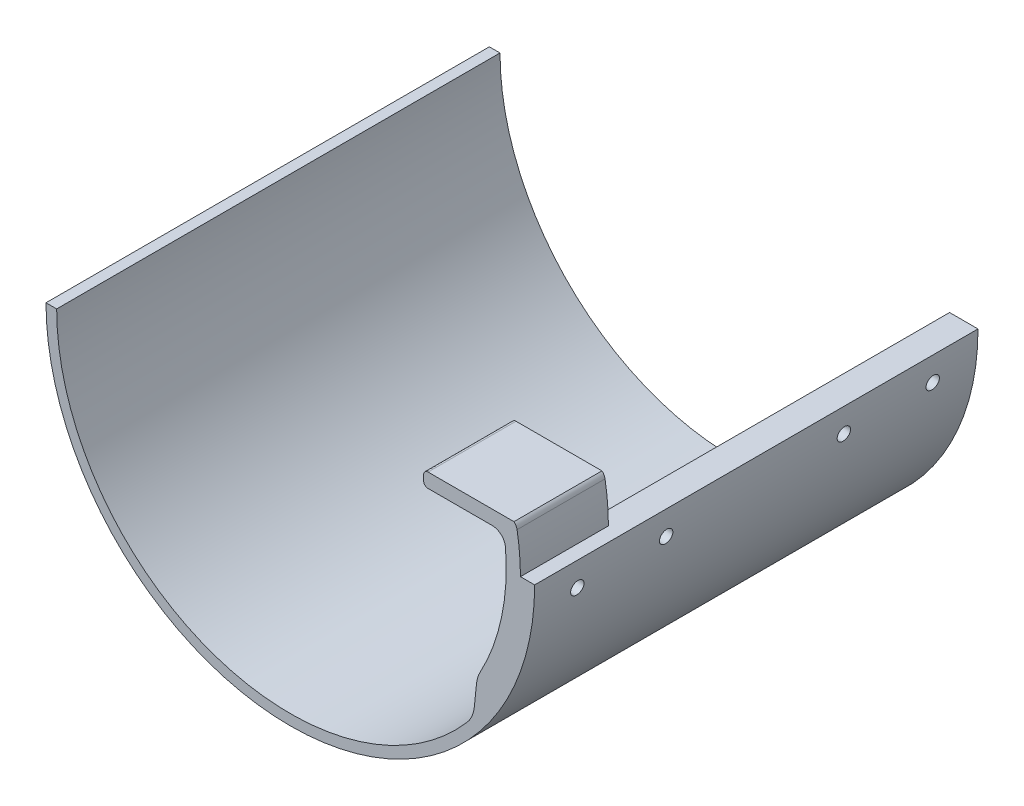
SolidWorks part; units mm, degrees
ref_plane "前视基准面" through (0, 0, 0) normal (0, 0, 1) x (1, 0, 0)
ref_plane "上视基准面" through (0, 0, 0) normal (0, 1, 0) x (1, 0, 0)
ref_plane "右视基准面" through (0, 0, 0) normal (1, 0, 0) x (0, 0, -1)
other "Configuration Table"
sketch "草图1" plane through (0, 0, 0) normal (0, 0, 1) x (1, 0, 0)
  line L0 (-55, 0) -> (-52.6, 0)
  line L1 (51.8, 0) -> (55, 0)
  line L2 (-52.6, 0) -> (51.8, 0) construction
  line L5 (41.9103, -25.796) -> (41.4208, -30.58)
  line L6 (0, 0) -> (0, 10) construction
  line L7 (0, 10) -> (31, 10) construction
  line L9 (30, 9) -> (30, 7.8)
  line L10 (31, 6.8) -> (45.4414, 6.8)
  line L11 (31, 10) -> (50.344, 10)
  arc A0 (-55, 0) -> (55, 0) centre (0, 0) ccw
  arc A1 (-52.6, 0) -> (39.7466, -34.4524) centre (0, 0) ccw
  arc A2 (51.0485, 8.7916) -> (51.8, 0) centre (0, 0) cw
  arc A3 (42.7207, -23.1711) -> (48.431, 4.05) centre (0, 0) ccw
  arc A4 (41.4208, -30.58) -> (39.7466, -34.4524) centre (34.4571, -29.8675) cw
  arc A5 (41.9103, -25.796) -> (42.7207, -23.1711) centre (48.8739, -26.5085) cw
  arc A6 (48.431, 4.05) -> (45.4414, 6.8) centre (45.4414, 3.8) ccw
  arc A7 (51.0485, 8.7916) -> (50.344, 10) centre (49.0775, 8.4521) ccw
  arc A8 (31, 6.8) -> (30, 7.8) centre (31, 7.8) cw
  arc A9 (30, 9) -> (31, 10) centre (31, 9) cw
  point P16 (42.0579, -24.3536)
  point P25 (52.0183, 10)
  point P28 (30, 6.8)
  point P31 (30.5845, 10)
  dimension "D1" = 110
  dimension "D2" = 105.2
  dimension "D3" = 97.2
  dimension "D6" = 7
  dimension "D9" = 3
  dimension "D10" = 2
  dimension "D11" = 1
  dimension "D12" = 1
  dimension "D14" = 51.8
  dimension "D5" = 31
  dimension "D7" = 3.2
  dimension "D8" = 21.4339
  dimension "D13" = 10
extrude "凸台-拉伸1" add sketch "草图1" along normal blind 99.8
sketch "草图4" plane through (0, 0, 99.8) normal (0, 0, 1) x (1, 0, 0)
  line L0 (55, 0) -> (0, 0)
  line L1 (0, 0) -> (50.017, 22.8758)
  arc A0 (55, 0) -> (50.017, 22.8758) centre (0, 0) ccw
sketch "草图5" plane through (0, 0, 0) normal (0, 0, -1) x (-1, 0, 0)
  line L0 (0, 0) -> (0, -5.5)
  line L1 (0, -5.5) -> (54.3615, -5.5)
  line L2 (0, 0) -> (54.3615, -5.5) construction
  line L3 (0, 0) -> (5.5, 54.3615) construction
  line L4 (0, 0) -> (0, 54.639) construction
  line L5 (0, 0) -> (-54.3615, -5.5) construction
  line L6 (0, 0) -> (-5.5, 54.3615) construction
  circle A0 centre (0, 0) radius 54.639
  dimension "D1" = 5.5
  dimension "D2" = 90
ref_plane "基准面1" through (0, 0, 0) normal (-0.9949, 0.1007, 0) x (0.1007, 0.9949, 0)
sketch "草图7" plane through (0, 0, 0) normal (-0.9949, 0.1007, 0) x (0.1007, 0.9949, 0)
  line L0 (-5.5363, -99.8) -> (-5.5363, 0) construction
  line L1 (-55, -99.8) -> (5.5363, -99.8) construction
  line L2 (-0.1363, 0) -> (-0.1363, -99.8) construction
  line L3 (54.639, 0) -> (-54.639, 0) construction
  line L4 (-5.4721, 0) -> (-10.9441, 0) construction
  circle A0 centre (-0.1363, -9.9) radius 1.5
  circle A1 centre (-0.1363, -29.9) radius 1.5
  circle A2 centre (-0.1363, -69.9) radius 1.5
  circle A3 centre (-0.1363, -89.9) radius 1.5
  dimension "D1" = 3
  dimension "D2" = 3
  dimension "D3" = 3
  dimension "D4" = 3
  dimension "D5" = 5.4
  dimension "D6" = 9.9
  dimension "D7" = 20
  dimension "D8" = 9.9
  dimension "D9" = 20
extrude "切除-拉伸6" cut sketch "草图7" against normal blind 80
sketch "草图8" plane through (0, 0, 0) normal (0, 0, -1) x (-1, 0, 0)
  line L0 (-55, 0) -> (0, 0) construction
  line L1 (-50.017, 22.8758) -> (0, 0)
  line L2 (0, 0) -> (-55, 0)
  arc A0 (-50.017, 22.8758) -> (-55, 0) centre (0, 0) ccw
extrude "切除-拉伸7" cut sketch "草图8" against normal blind 80
